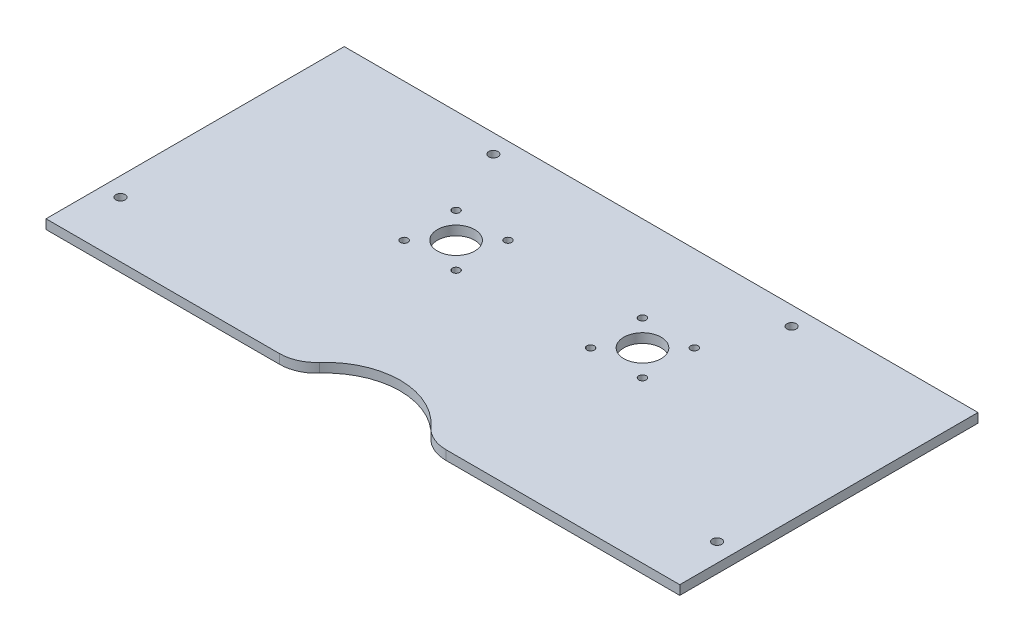
SolidWorks part; units mm, degrees
material "6061-T6 (SS)"
ref_plane "Front Plane" through (0, 0, 0) normal (0, 0, 1) x (1, 0, 0)
ref_plane "Top Plane" through (0, 0, 0) normal (0, 1, 0) x (1, 0, 0)
ref_plane "Right Plane" through (0, 0, 0) normal (1, 0, 0) x (0, 0, -1)
sketch "Sketch1" plane through (0, 0, 0) normal (0, 1, 0) x (1, 0, 0)
  line L0 (0, 101.6) -> (0, 0)
  line L1 (0, 0) -> (215.9, 0)
  line L2 (0, 0) -> (0, 228.6)
  line L3 (0, 228.6) -> (215.9, 228.6)
  line L4 (215.9, 0) -> (215.9, 228.6)
  line L5 (0, 127) -> (85.953, 127)
  line L6 (0, 127) -> (0, 101.6)
  line L7 (0, 101.6) -> (85.953, 101.6)
  line L8 (85.953, 127) -> (85.953, 101.6)
  line L9 (215.9, 127) -> (129.947, 127)
  line L10 (215.9, 127) -> (215.9, 101.6)
  line L11 (215.9, 101.6) -> (129.947, 101.6)
  line L12 (129.947, 127) -> (129.947, 101.6)
  line L13 (215.9, 0) -> (215.9, 101.6)
  circle A0 centre (107.95, 114.3) radius 25.4
  point P13 (85.953, 114.3)
  point P18 (0, 114.3)
  dimension "D4" = 50.8
  dimension "D5" = 85.953
  dimension "D1" = 228.6
  dimension "D2" = 215.9
  dimension "D3" = 25.4
extrude "Boss-Extrude1" add sketch "Sketch1" along normal blind 3.175 contours A0 L9 L4 L3 L2 L5 region at (107.95, 0, -178.6387)
sketch "Sketch2" plane through (0, 3.175, 0) normal (0, 1, 0) x (1, 0, 0)
  line L0 (0, 190.5) -> (76.2, 190.5) construction
  line L2 (76.2, 190.5) -> (139.7, 190.5) construction
  line L3 (0, 228.6) -> (215.9, 228.6) construction
  line L4 (215.9, 127) -> (215.9, 228.6) construction
  line L5 (139.7, 190.5) -> (215.9, 190.5) construction
  line L8 (0, 127) -> (0, 228.6) construction
  circle A0 centre (76.2, 190.5) radius 6.35
  circle A1 centre (139.7, 190.5) radius 6.35
  dimension "D1" = 12.7
  dimension "D2" = 38.1
  dimension "D3" = 63.5
extrude "Cut-Extrude1" cut sketch "Sketch2" against normal through all
fillet "Fillet1" radius 12.7 2 edges at (129.947, 1.5875, -127) (85.953, 1.5875, -127)
sketch "Sketch3" plane through (0, 3.175, 0) normal (0, 1, 0) x (1, 0, 0)
  line L1 (67.3612, 181.6612) -> (85.0388, 181.6612) construction
  line L2 (67.3612, 181.6612) -> (67.3612, 199.3388) construction
  line L3 (67.3612, 199.3388) -> (85.0388, 199.3388) construction
  line L4 (85.0388, 181.6612) -> (85.0388, 199.3388) construction
  line L5 (67.3612, 181.6612) -> (85.0388, 199.3388) construction
  line L6 (67.3612, 199.3388) -> (85.0388, 181.6612) construction
  line L7 (130.8612, 181.6612) -> (148.5388, 181.6612) construction
  line L8 (130.8612, 181.6612) -> (130.8612, 199.3388) construction
  line L9 (130.8612, 199.3388) -> (148.5388, 199.3388) construction
  line L10 (148.5388, 181.6612) -> (148.5388, 199.3388) construction
  line L11 (130.8612, 181.6612) -> (148.5388, 199.3388) construction
  line L12 (130.8612, 199.3388) -> (148.5388, 181.6612) construction
  circle A0 centre (85.0388, 199.3388) radius 1.27
  circle A1 centre (67.3612, 181.6612) radius 1.27
  circle A2 centre (67.3612, 199.3388) radius 1.27
  circle A3 centre (85.0388, 181.6612) radius 1.27
  circle A4 centre (130.8612, 181.6612) radius 1.27
  circle A5 centre (148.5388, 181.6612) radius 1.27
  circle A6 centre (148.5388, 199.3388) radius 1.27
  circle A7 centre (130.8612, 199.3388) radius 1.27
  point P0 (76.2, 190.5)
  point P6 (139.7, 190.5)
  dimension "D2" = 2.54
  dimension "D1" = 25
extrude "Cut-Extrude2" cut sketch "Sketch3" against normal through all
sketch "Sketch4" plane through (0, 3.175, 0) normal (0, 1, 0) x (1, 0, 0)
  line L0 (0, 127) -> (0, 228.6) construction
  line L1 (0, 127) -> (79.5519, 127) construction
  line L2 (215.9, 127) -> (136.3481, 127) construction
  line L3 (215.9, 127) -> (215.9, 228.6) construction
  line L4 (0, 228.6) -> (215.9, 228.6) construction
  circle A0 centre (6.35, 146.05) radius 1.5875
  circle A1 centre (57.15, 222.25) radius 1.5875
  circle A2 centre (158.75, 222.25) radius 1.5875
  circle A3 centre (209.55, 146.05) radius 1.5875
  dimension "D1" = 3.175
  dimension "D2" = 6.35
  dimension "D3" = 19.05
  dimension "D4" = 19.05
  dimension "D5" = 6.35
  dimension "D6" = 57.15
  dimension "D7" = 6.35
  dimension "D8" = 6.35
  dimension "D9" = 57.15
extrude "Cut-Extrude3" cut sketch "Sketch4" against normal through all
